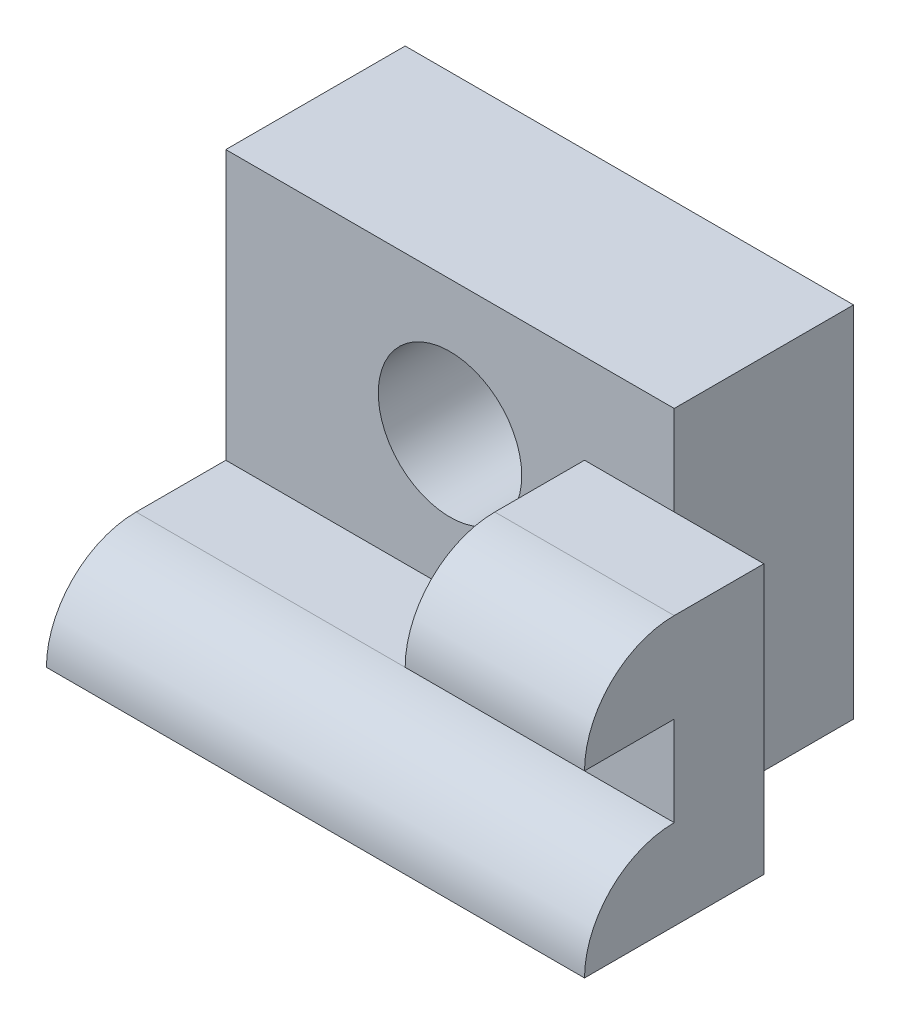
SolidWorks part; units mm, degrees
ref_plane "Front Plane" through (0, 0, 0) normal (0, 0, 1) x (1, 0, 0)
ref_plane "Top Plane" through (0, 0, 0) normal (0, 1, 0) x (1, 0, 0)
ref_plane "Right Plane" through (0, 0, 0) normal (1, 0, 0) x (0, 0, -1)
sketch "Sketch1" plane through (0, 0, 0) normal (1, 0, 0) x (0, 0, -1)
  line L0 (0, 0) -> (40, 0)
  line L1 (40, 0) -> (40, 40)
  line L2 (40, 40) -> (20, 40)
  line L3 (20, 40) -> (20, 30)
  line L4 (20, 30) -> (0, 30)
  line L5 (0, 30) -> (0, 20)
  line L6 (0, 20) -> (10, 20)
  line L7 (10, 20) -> (10, 10)
  line L8 (10, 10) -> (0, 10)
  line L9 (0, 10) -> (0, 0)
  line L10 (20, 30) -> (20, 0)
  line L11 (10, 10) -> (20, 10)
  dimension "D1" = 40
  dimension "D2" = 20
  dimension "D3" = 20
  dimension "D4" = 10
  dimension "D5" = 10
  dimension "D6" = 10
  dimension "D7" = 10
  dimension "D8" = 10
  dimension "D9" = 30
  dimension "D10" = 10
extrude "Boss-Extrude3" add sketch "Sketch1" against normal blind 60 contours L11 L8 L9 L0 L10 region at (0, 5, -10)
extrude "Boss-Extrude4" add sketch "Sketch1<7>" against normal blind 20 contours L7 L11 L10 L4 L5 L6 region at (0, 21.6667, -11.6667)
sketch "Sketch1<7>" plane through (0, 0, 0) normal (1, 0, 0) x (0, 0, -1) same geometry as "Sketch1"
extrude "Boss-Extrude5" add sketch "Sketch1<8>" against normal blind 60 contours L3 L10 L0 L1 L2 region at (0, 20, -30)
sketch "Sketch1<8>" plane through (0, 0, 0) normal (1, 0, 0) x (0, 0, -1) same geometry as "Sketch1"
extrude "Cut-Extrude2" cut sketch "Sketch1<9>" against normal blind 10 contours L3 L10 L0 L1 L2 region at (0, 20, -30)
sketch "Sketch1<9>" plane through (0, 0, 0) normal (1, 0, 0) x (0, 0, -1) same geometry as "Sketch1"
fillet "Fillet1" radius 10 1 edges at (-30, 10, 0)
fillet "Fillet2" radius 10 1 edges at (-10, 30, 0)
sketch "Sketch3" plane through (0, 0, -20) normal (0, 0, 1) x (1, 0, 0)
  line L0 (-60, 40) -> (-60, 10) construction
  line L1 (-60, 40) -> (-10, 40) construction
  circle A0 centre (-35, 25) radius 8
  dimension "D1" = 16
  dimension "D2" = 25
  dimension "D3" = 15
extrude "Cut-Extrude3" cut sketch "Sketch3" against normal blind 36
